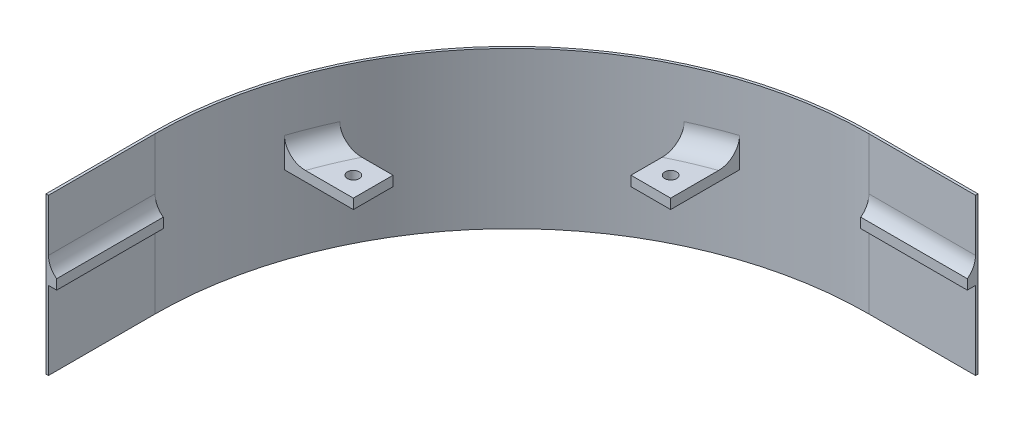
SolidWorks part; units mm, degrees
ref_plane "Front Plane" through (0, 0, 0) normal (0, 0, 1) x (1, 0, 0)
ref_plane "Top Plane" through (0, 0, 0) normal (0, 1, 0) x (1, 0, 0)
ref_plane "Right Plane" through (0, 0, 0) normal (1, 0, 0) x (0, 0, -1)
sketch "Sketch1" plane through (0, 0, 0) normal (0, 1, 0) x (1, 0, 0)
  line L1 (-34.1312, -148.4312) -> (34.1313, -148.4312)
  line L2 (-148.4312, -34.1312) -> (-148.4312, 34.1313)
  line L3 (-34.1312, 148.4313) -> (34.1313, 148.4313)
  line L4 (148.4312, -34.1312) -> (148.4312, 34.1313)
  line L5 (-148.4312, -148.4312) -> (148.4313, 148.4312) construction
  line L6 (-148.4312, 148.4312) -> (148.4313, -148.4312) construction
  arc A1 (-34.1312, -148.4312) -> (-148.4312, -34.1312) centre (-34.1312, -34.1312) cw
  arc A2 (34.1313, -148.4312) -> (148.4312, -34.1312) centre (34.1313, -34.1312) ccw
  arc A3 (34.1313, 148.4313) -> (148.4312, 34.1313) centre (34.1313, 34.1313) cw
  arc A4 (-148.4312, 34.1313) -> (-34.1312, 148.4313) centre (-34.1312, 34.1313) cw
  point P0 (0, 0)
  dimension "D1" = 296.8625
  dimension "D3" = 114.3
  dimension "D2" = 296.8625
extrude "Boss-Extrude1" add sketch "Sketch1" along normal blind 6.35
sketch "Sketch4" plane through (0, 6.35, 0) normal (0, 1, 0) x (1, 0, 0)
  line L0 (-39.448, -144.217) -> (39.448, -144.217)
  line L1 (-39.448, -120.2902) -> (39.448, -120.2902)
  line L2 (-39.448, 120.2902) -> (39.448, 120.2902)
  line L3 (-39.448, 144.217) -> (39.448, 144.217)
  line L4 (-39.448, 118.7027) -> (39.448, 118.7027)
  line L5 (-39.448, 145.8045) -> (39.448, 145.8045)
  line L6 (-39.448, -145.8045) -> (39.448, -145.8045)
  line L7 (-39.448, -118.7027) -> (39.448, -118.7027)
  line L8 (-13.125, 107.0625) -> (-13.125, 100.3125) construction
  line L9 (-13.125, 100.3125) -> (-18.875, 100.3125) construction
  line L10 (-18.875, 100.3125) -> (-18.875, 107.0625) construction
  line L11 (-18.875, 107.0625) -> (-13.125, 107.0625) construction
  line L12 (18.875, 107.0625) -> (18.875, 100.3125) construction
  line L13 (18.875, 100.3125) -> (13.125, 100.3125) construction
  line L14 (13.125, 100.3125) -> (13.125, 107.0625) construction
  line L15 (13.125, 107.0625) -> (18.875, 107.0625) construction
  line L16 (-7, 56.325) -> (-13, 56.325) construction
  line L17 (-13, 56.325) -> (-13, 64.325) construction
  line L18 (-13, 64.325) -> (-7, 64.325) construction
  line L19 (-7, 64.325) -> (-7, 56.325) construction
  line L20 (25, 56.325) -> (19, 56.325) construction
  line L21 (19, 56.325) -> (19, 64.325) construction
  line L22 (19, 64.325) -> (25, 64.325) construction
  line L23 (25, 64.325) -> (25, 56.325) construction
  line L24 (-13, -56.325) -> (-7, -56.325) construction
  line L25 (-7, -56.325) -> (-7, -64.325) construction
  line L26 (-7, -64.325) -> (-13, -64.325) construction
  line L27 (-13, -64.325) -> (-13, -56.325) construction
  line L28 (19, -56.325) -> (25, -56.325) construction
  line L29 (25, -56.325) -> (25, -64.325) construction
  line L30 (25, -64.325) -> (19, -64.325) construction
  line L31 (19, -64.325) -> (19, -56.325) construction
  line L32 (-18.875, -107.0625) -> (-18.875, -100.3125) construction
  line L33 (-18.875, -100.3125) -> (-13.125, -100.3125) construction
  line L34 (-13.125, -100.3125) -> (-13.125, -107.0625) construction
  line L35 (-13.125, -107.0625) -> (-18.875, -107.0625) construction
  line L36 (13.125, -107.0625) -> (13.125, -100.3125) construction
  line L37 (13.125, -100.3125) -> (18.875, -100.3125) construction
  line L38 (18.875, -100.3125) -> (18.875, -107.0625) construction
  line L39 (18.875, -107.0625) -> (13.125, -107.0625) construction
  line L40 (-13.125, 107.0625) -> (-13.125, 100.3125)
  line L41 (-13.125, 100.3125) -> (-18.875, 100.3125)
  line L42 (-18.875, 100.3125) -> (-18.875, 107.0625)
  line L43 (-18.875, 107.0625) -> (-13.125, 107.0625)
  line L44 (18.875, 107.0625) -> (18.875, 100.3125)
  line L45 (18.875, 100.3125) -> (13.125, 100.3125)
  line L46 (13.125, 100.3125) -> (13.125, 107.0625)
  line L47 (13.125, 107.0625) -> (18.875, 107.0625)
  line L48 (-7, 56.325) -> (-13, 56.325)
  line L49 (-13, 56.325) -> (-13, 64.325)
  line L50 (-13, 64.325) -> (-7, 64.325)
  line L51 (-7, 64.325) -> (-7, 56.325)
  line L52 (25, 56.325) -> (19, 56.325)
  line L53 (19, 56.325) -> (19, 64.325)
  line L54 (19, 64.325) -> (25, 64.325)
  line L55 (25, 64.325) -> (25, 56.325)
  line L56 (-13, -56.325) -> (-7, -56.325)
  line L57 (-7, -56.325) -> (-7, -64.325)
  line L58 (-7, -64.325) -> (-13, -64.325)
  line L59 (-13, -64.325) -> (-13, -56.325)
  line L60 (19, -56.325) -> (25, -56.325)
  line L61 (25, -56.325) -> (25, -64.325)
  line L62 (25, -64.325) -> (19, -64.325)
  line L63 (19, -64.325) -> (19, -56.325)
  line L64 (-18.875, -107.0625) -> (-18.875, -100.3125)
  line L65 (-18.875, -100.3125) -> (-13.125, -100.3125)
  line L66 (-13.125, -100.3125) -> (-13.125, -107.0625)
  line L67 (-13.125, -107.0625) -> (-18.875, -107.0625)
  line L68 (13.125, -107.0625) -> (13.125, -100.3125)
  line L69 (13.125, -100.3125) -> (18.875, -100.3125)
  line L70 (18.875, -100.3125) -> (18.875, -107.0625)
  line L71 (18.875, -107.0625) -> (13.125, -107.0625)
  line L72 (-18.875, -107.0625) -> (-13.125, -100.3125) construction
  line L73 (13.125, -107.0625) -> (18.875, -100.3125) construction
  line L74 (-13, -64.325) -> (-7, -56.325) construction
  line L75 (19, -64.325) -> (25, -56.325) construction
  line L76 (-13, 56.325) -> (-7, 64.325) construction
  line L77 (19, 56.325) -> (25, 64.325) construction
  line L78 (13.125, 100.3125) -> (18.875, 107.0625) construction
  line L79 (-18.875, 100.3125) -> (-13.125, 107.0625) construction
  arc A0 (58.6792, -125.8296) -> (39.448, -120.2902) centre (39.448, -156.4424) ccw construction
  arc A1 (58.6792, -138.6776) -> (58.6792, -125.8296) centre (54.6436, -132.2536) ccw construction
  arc A2 (39.448, -144.217) -> (58.6792, -138.6776) centre (39.448, -108.0647) ccw construction
  arc A3 (-39.448, -120.2902) -> (-58.6792, -125.8296) centre (-39.448, -156.4424) ccw construction
  arc A4 (-58.6792, -125.8296) -> (-58.6792, -138.6776) centre (-54.6436, -132.2536) ccw construction
  arc A5 (-58.6792, -138.6776) -> (-39.448, -144.217) centre (-39.448, -108.0647) ccw construction
  arc A6 (-58.6792, 125.8296) -> (-39.448, 120.2902) centre (-39.448, 156.4424) ccw construction
  arc A7 (-58.6792, 138.6776) -> (-58.6792, 125.8296) centre (-54.6436, 132.2536) ccw construction
  arc A8 (-39.448, 144.217) -> (-58.6792, 138.6776) centre (-39.448, 108.0647) ccw construction
  arc A9 (58.6792, 138.6776) -> (39.448, 144.217) centre (39.448, 108.0647) ccw construction
  arc A10 (58.6792, 125.8296) -> (58.6792, 138.6776) centre (54.6436, 132.2536) ccw construction
  arc A11 (39.448, 120.2902) -> (58.6792, 125.8296) centre (39.448, 156.4424) ccw construction
  arc A12 (58.6792, -125.8296) -> (39.448, -120.2902) centre (39.448, -156.4424) ccw
  arc A13 (58.6792, -138.6776) -> (58.6792, -125.8296) centre (54.6436, -132.2536) ccw
  arc A14 (39.448, -144.217) -> (58.6792, -138.6776) centre (39.448, -108.0647) ccw
  arc A15 (-39.448, -120.2902) -> (-58.6792, -125.8296) centre (-39.448, -156.4424) ccw
  arc A16 (-58.6792, -125.8296) -> (-58.6792, -138.6776) centre (-54.6436, -132.2536) ccw
  arc A17 (-58.6792, -138.6776) -> (-39.448, -144.217) centre (-39.448, -108.0647) ccw
  arc A18 (-58.6792, 125.8296) -> (-39.448, 120.2902) centre (-39.448, 156.4424) ccw
  arc A19 (-58.6792, 138.6776) -> (-58.6792, 125.8296) centre (-54.6436, 132.2536) ccw
  arc A20 (-39.448, 144.217) -> (-58.6792, 138.6776) centre (-39.448, 108.0647) ccw
  arc A21 (58.6792, 138.6776) -> (39.448, 144.217) centre (39.448, 108.0647) ccw
  arc A22 (58.6792, 125.8296) -> (58.6792, 138.6776) centre (54.6436, 132.2536) ccw
  arc A23 (39.448, 120.2902) -> (58.6792, 125.8296) centre (39.448, 156.4424) ccw
  arc A24 (-59.5236, 124.4853) -> (-39.448, 118.7027) centre (-39.448, 156.4424) ccw
  arc A25 (39.448, 118.7027) -> (59.5236, 124.4853) centre (39.448, 156.4424) ccw
  arc A26 (59.5236, 124.4853) -> (59.5236, 140.0219) centre (54.6436, 132.2536) ccw
  arc A27 (59.5236, 140.0219) -> (39.448, 145.8045) centre (39.448, 108.0647) ccw
  arc A28 (-39.448, 145.8045) -> (-59.5236, 140.0219) centre (-39.448, 108.0647) ccw
  arc A29 (-59.5236, 140.0219) -> (-59.5236, 124.4853) centre (-54.6436, 132.2536) ccw
  arc A30 (39.448, -145.8045) -> (59.5236, -140.0219) centre (39.448, -108.0647) ccw
  arc A31 (59.5236, -140.0219) -> (59.5236, -124.4853) centre (54.6436, -132.2536) ccw
  arc A32 (59.5236, -124.4853) -> (39.448, -118.7027) centre (39.448, -156.4424) ccw
  arc A33 (-39.448, -118.7027) -> (-59.5236, -124.4853) centre (-39.448, -156.4424) ccw
  arc A34 (-59.5236, -124.4853) -> (-59.5236, -140.0219) centre (-54.6436, -132.2536) ccw
  arc A35 (-59.5236, -140.0219) -> (-39.448, -145.8045) centre (-39.448, -108.0647) ccw
  point P58 (-16, -103.6875)
  point P60 (16, 103.6875)
  point P62 (-16, 103.6875)
  point P63 (-10, 60.325)
  point P66 (22, 60.325)
  point P68 (-10, -60.325)
  point P70 (16, -103.6875)
  point P71 (22, -60.325)
  dimension "D1" = 1.5875
extrude "Cut-Extrude1" cut sketch "Sketch4" against normal blind 6.35 contours L2 A23 A22 A21 L3 A20 A19 A18 | A28 A29 A24 L4 A25 A26 A27 L5 A23 L2 A18 A19 A20 L3 A21 A22 | A16 A17 L0 A14 A13 A12 L1 A15 | A34 A35 L6 A30 A31 A32 L7 A33 A17 A16 A15 L1 A12 A13 A14 L0 region at (0, 6.35, 132.2536) region at (0, 6.35, -132.2536) region at (-49.5328, 6.35, -121.431) region at (-49.5328, 6.35, 143.0762)
hole_wizard "M4 Clearance Hole1" positions "Sketch7" profile "Sketch9" hole size "M4" standard "ANSI Metric" end condition through all
sketch "Sketch7" plane through (0, 6.35, 0) normal (0, 1, 0) x (1, 0, 0)
  point P0 (-16, -103.6875)
  point P3 (16, -103.6875)
  point P6 (22, -60.325)
  point P9 (-10, -60.325)
  point P12 (-10, 60.325)
  point P15 (22, 60.325)
  point P18 (16, 103.6875)
  point P21 (-16, 103.6875)
sketch "Sketch9" plane through (-16, 6.35, 103.6875) normal (1, 0, 0) x (0, 0, 1)
  line L0 (0, 0) -> (0, 6.35)
  line L1 (0, 6.35) -> (2.25, 6.35)
  line L2 (2.25, 6.35) -> (2.25, 0)
  line L5 (2.25, 0) -> (0, 0)
  line L11 (0, -6.35) -> (0, 107.95) construction
  dimension "Thru Hole Dia." = 4.5
  dimension "Thru Hole Depth" = 6.35
sketch "Sketch11" plane through (0, 6.35, 0) normal (0, 1, 0) x (1, 0, 0)
  line L1 (101.6, 101.6) -> (-101.6, 101.6)
  line L2 (101.6, 101.6) -> (101.6, -101.6)
  line L3 (101.6, -101.6) -> (-101.6, -101.6)
  line L4 (-101.6, 101.6) -> (-101.6, -101.6)
  line L5 (101.6, 101.6) -> (-101.6, -101.6) construction
  line L6 (101.6, -101.6) -> (-101.6, 101.6) construction
  circle A0 centre (0, 0) radius 143.6841 construction
  point P7 (-127, -101.6)
  point P10 (-127, 101.6)
  point P11 (-127, -76.2)
  point P12 (-127, -50.8)
  point P13 (-127, -25.4)
  point P14 (-127, 0)
  point P15 (-127, 25.4)
  point P16 (-127, 50.8)
  point P17 (-127, 76.2)
  point P18 (-101.6, -101.6)
  point P19 (-101.6, 101.6)
  point P20 (-101.6, -76.2)
  point P21 (-101.6, -50.8)
  point P22 (-101.6, -25.4)
  point P23 (-101.6, 0)
  point P24 (-101.6, 25.4)
  point P25 (-101.6, 50.8)
  point P26 (-101.6, 76.2)
  point P27 (-76.2, -101.6)
  point P28 (-76.2, 101.6)
  point P29 (-76.2, -76.2)
  point P30 (-76.2, -50.8)
  point P31 (-76.2, -25.4)
  point P32 (-76.2, 0)
  point P33 (-76.2, 25.4)
  point P34 (-76.2, 50.8)
  point P35 (-76.2, 76.2)
  point P36 (-50.8, -101.6)
  point P37 (-50.8, 101.6)
  point P38 (-50.8, -76.2)
  point P39 (-50.8, -50.8)
  point P40 (-50.8, -25.4)
  point P41 (-50.8, 0)
  point P42 (-50.8, 25.4)
  point P43 (-50.8, 50.8)
  point P44 (-50.8, 76.2)
  point P45 (-25.4, -101.6)
  point P46 (-25.4, 101.6)
  point P47 (-25.4, -76.2)
  point P48 (-25.4, -50.8)
  point P49 (-25.4, -25.4)
  point P50 (-25.4, 0)
  point P51 (-25.4, 25.4)
  point P52 (-25.4, 50.8)
  point P53 (-25.4, 76.2)
  point P54 (0, -101.6)
  point P55 (0, 101.6)
  point P56 (0, -76.2)
  point P57 (0, -50.8)
  point P58 (0, -25.4)
  point P59 (0, 0)
  point P60 (0, 25.4)
  point P61 (0, 50.8)
  point P62 (0, 76.2)
  point P63 (25.4, -101.6)
  point P64 (25.4, 101.6)
  point P65 (25.4, -76.2)
  point P66 (25.4, -50.8)
  point P67 (25.4, -25.4)
  point P68 (25.4, 0)
  point P69 (25.4, 25.4)
  point P70 (25.4, 50.8)
  point P71 (25.4, 76.2)
  point P72 (50.8, -101.6)
  point P73 (50.8, 101.6)
  point P74 (50.8, -76.2)
  point P75 (50.8, -50.8)
  point P76 (50.8, -25.4)
  point P77 (50.8, 0)
  point P78 (50.8, 25.4)
  point P79 (50.8, 50.8)
  point P80 (50.8, 76.2)
  point P81 (76.2, -101.6)
  point P82 (76.2, 101.6)
  point P83 (76.2, -76.2)
  point P84 (76.2, -50.8)
  point P85 (76.2, -25.4)
  point P86 (76.2, 0)
  point P87 (76.2, 25.4)
  point P88 (76.2, 50.8)
  point P89 (76.2, 76.2)
  point P90 (101.6, -101.6)
  point P91 (101.6, 101.6)
  point P92 (101.6, -76.2)
  point P93 (101.6, -50.8)
  point P94 (101.6, -25.4)
  point P95 (101.6, 0)
  point P96 (101.6, 25.4)
  point P97 (101.6, 50.8)
  point P98 (101.6, 76.2)
  point P99 (127, -101.6)
  point P100 (127, 101.6)
  point P101 (127, -76.2)
  point P102 (127, -50.8)
  point P103 (127, -25.4)
  point P104 (127, 0)
  point P105 (127, 25.4)
  point P106 (127, 50.8)
  point P107 (127, 76.2)
  dimension "D1" = 203.2
  dimension "D2" = 25.4
  dimension "D3" = 11
  dimension "D4" = 9
hole_wizard "#6 Clearance Hole1" positions "Sketch12" profile "Sketch13" hole size "#6" standard "ANSI Inch" end condition through all
sketch "Sketch12" plane through (0, 6.35, 0) normal (0, 1, 0) x (1, 0, 0)
  point P0 (-101.6, -101.6)
  point P3 (-101.6, 101.6)
  point P6 (101.6, 101.6)
  point P9 (101.6, -101.6)
  point P12 (-127, -76.2)
  point P15 (-127, -50.8)
  point P18 (-127, 50.8)
  point P21 (-127, 76.2)
  point P24 (-101.6, 76.2)
  point P27 (-101.6, 50.8)
  point P30 (-101.6, 25.4)
  point P33 (-101.6, 0)
  point P36 (-101.6, -25.4)
  point P39 (-101.6, -50.8)
  point P42 (-101.6, -76.2)
  point P45 (-76.2, -101.6)
  point P48 (-50.8, -101.6)
  point P51 (-50.8, -76.2)
  point P54 (-76.2, -76.2)
  point P57 (-76.2, -50.8)
  point P60 (-50.8, -50.8)
  point P63 (-50.8, -25.4)
  point P66 (-76.2, -25.4)
  point P69 (-76.2, 0)
  point P72 (-50.8, 0)
  point P75 (-50.8, 25.4)
  point P78 (-76.2, 25.4)
  point P81 (-76.2, 50.8)
  point P84 (-50.8, 50.8)
  point P87 (-50.8, 76.2)
  point P90 (-76.2, 76.2)
  point P93 (-76.2, 101.6)
  point P96 (-50.8, 101.6)
  point P99 (50.8, -101.6)
  point P102 (76.2, -101.6)
  point P105 (101.6, -76.2)
  point P108 (127, -76.2)
  point P111 (127, -50.8)
  point P114 (101.6, -25.4)
  point P117 (101.6, -50.8)
  point P120 (76.2, -25.4)
  point P123 (76.2, -50.8)
  point P126 (76.2, -76.2)
  point P129 (50.8, -76.2)
  point P132 (50.8, -50.8)
  point P135 (50.8, -25.4)
  point P138 (50.8, 0)
  point P141 (76.2, 0)
  point P144 (101.6, 0)
  point P147 (101.6, 25.4)
  point P150 (101.6, 50.8)
  point P153 (101.6, 76.2)
  point P156 (127, 50.8)
  point P159 (127, 76.2)
  point P162 (76.2, 101.6)
  point P165 (50.8, 101.6)
  point P168 (50.8, 76.2)
  point P171 (76.2, 76.2)
  point P174 (76.2, 50.8)
  point P177 (76.2, 25.4)
  point P180 (50.8, 25.4)
  point P183 (50.8, 50.8)
  point P186 (0, 0)
  point P189 (-25.4, -25.4)
  point P192 (-25.4, 0)
  point P195 (-25.4, 25.4)
  point P198 (0, 25.4)
  point P201 (25.4, 25.4)
  point P204 (25.4, 0)
  point P207 (25.4, -25.4)
  point P210 (0, -25.4)
  point P213 (127, -25.4)
  point P216 (127, 0)
  point P219 (127, 25.4)
  point P222 (-127, -25.4)
  point P225 (-127, 0)
  point P228 (-127, 25.4)
sketch "Sketch13" plane through (-101.6, 6.35, 101.6) normal (1, 0, 0) x (0, 0, 1)
  line L0 (0, 0) -> (0, 6.35)
  line L1 (0, 6.35) -> (1.8986, 6.35)
  line L2 (1.8986, 6.35) -> (1.8986, 0)
  line L5 (1.8986, 0) -> (0, 0)
  line L11 (0, -6.35) -> (0, 107.95) construction
  dimension "Thru Hole Dia." = 3.7973
  dimension "Thru Hole Depth" = 6.35
sketch "Sketch14" plane through (0, 6.35, 0) normal (0, 1, 0) x (1, 0, 0)
  line L1 (76.2, -127) -> (-76.2, -127)
  line L2 (76.2, -127) -> (76.2, 127)
  line L3 (76.2, 127) -> (-76.2, 127)
  line L4 (-76.2, -127) -> (-76.2, 127)
  line L5 (76.2, -127) -> (-76.2, 127) construction
  line L6 (76.2, 127) -> (-76.2, -127) construction
  circle A1 centre (-76.2, -101.6) radius 1.8986 construction
  circle A2 centre (-101.6, -101.6) radius 1.8986 construction
  point P0 (0, 0)
  dimension "D1" = 25.4
  dimension "D2" = 25.4
hole_wizard "#6 Clearance Hole2" positions "Sketch15" profile "Sketch16" hole size "#6" standard "ANSI Inch" end condition through all
sketch "Sketch15" plane through (0, 6.35, 0) normal (0, 1, 0) x (1, 0, 0)
  point P0 (-76.2, -127)
  point P3 (76.2, -127)
  point P6 (76.2, 127)
  point P9 (-76.2, 127)
sketch "Sketch16" plane through (-76.2, 6.35, 127) normal (1, 0, 0) x (0, 0, 1)
  line L0 (0, 0) -> (0, 6.35)
  line L1 (0, 6.35) -> (1.8986, 6.35)
  line L2 (1.8986, 6.35) -> (1.8986, 0)
  line L5 (1.8986, 0) -> (0, 0)
  line L11 (0, -6.35) -> (0, 107.95) construction
  dimension "Thru Hole Dia." = 3.7973
  dimension "Thru Hole Depth" = 6.35
sketch "Sketch29" plane through (0, 6.35, 0) normal (0, 1, 0) x (1, 0, 0)
  line L0 (-39.448, 145.8045) -> (39.448, 145.8045) construction
  line L1 (-148.4312, 34.1312) -> (-148.4312, -34.1312) construction
  line L2 (-34.1312, 148.4313) -> (0, 148.4313)
  line L3 (34.1313, 148.4313) -> (-34.1312, 148.4313) construction
  line L4 (-148.4312, 34.1312) -> (-148.4312, 0)
  line L5 (0, 148.4313) -> (-34.1312, 148.4313)
  line L6 (-69.85, 142.7068) -> (-69.85, 120.65)
  line L7 (-69.85, 120.65) -> (-82.55, 120.65)
  line L8 (-82.55, 120.65) -> (-82.55, 137.6692)
  line L9 (-137.6692, 82.55) -> (-120.65, 82.55)
  line L10 (-34.1312, -148.4312) -> (34.1313, -148.4312)
  line L11 (148.4313, -34.1312) -> (148.4312, 34.1313)
  line L12 (34.1313, 148.4313) -> (-34.1312, 148.4313)
  line L13 (-148.4312, 34.1312) -> (-148.4312, -34.1312)
  line L14 (-34.1312, 148.4313) -> (-34.1312, 145.8045)
  line L15 (-34.1312, 145.8045) -> (0, 145.8045)
  line L16 (0, 148.4313) -> (-34.1312, 148.4313)
  line L17 (-148.4312, 34.1312) -> (-148.4312, 0)
  line L18 (-120.65, 82.55) -> (-120.65, 69.85)
  line L19 (-120.65, 69.85) -> (-142.7068, 69.85)
  line L20 (0, 149.225) -> (-34.1312, 149.225)
  line L21 (-149.225, 34.1312) -> (-149.225, 0)
  line L22 (0, 148.4313) -> (0, 149.225)
  line L23 (-148.4312, 0) -> (-149.225, 0)
  line L24 (34.1313, 149.225) -> (-34.1312, 149.225) construction
  line L25 (34.1313, 148.4313) -> (-34.1312, 148.4313) construction
  line L26 (-149.225, 34.1312) -> (-149.225, -34.1312) construction
  line L27 (-148.4312, 34.1312) -> (-148.4312, -34.1312) construction
  line L28 (0, 148.4313) -> (0, 145.8045)
  line L30 (-148.4312, 34.1312) -> (-145.8045, 34.1312)
  line L31 (-148.4312, 34.1312) -> (-148.4312, 0)
  line L32 (-148.4312, 0) -> (-145.8045, 0)
  line L33 (-145.8045, 34.1312) -> (-145.8045, 0)
  arc A0 (-34.1312, 148.4313) -> (-148.4312, 34.1312) centre (-34.1312, 34.1313) ccw construction
  arc A1 (-34.1312, 148.4313) -> (-69.85, 142.7068) centre (-34.1312, 34.1313) ccw
  circle A2 centre (-127, 76.2) radius 1.8987 construction
  circle A3 centre (-76.2, 127) radius 1.8987 construction
  circle A4 centre (-127, 76.2) radius 1.8987
  circle A5 centre (-76.2, 127) radius 1.8987
  arc A6 (-34.1312, 149.225) -> (-149.225, 34.1313) centre (-34.1312, 34.1313) ccw
  arc A7 (-82.55, 137.6692) -> (-137.6692, 82.55) centre (-34.1312, 34.1313) ccw
  arc A8 (-34.1312, 148.4313) -> (-148.4312, 34.1312) centre (-34.1312, 34.1313) ccw construction
  arc A9 (-82.55, 137.6692) -> (-137.6692, 82.55) centre (-34.1312, 34.1313) ccw
  arc A10 (-148.4312, -34.1312) -> (-34.1312, -148.4312) centre (-34.1312, -34.1312) ccw
  arc A11 (34.1313, -148.4312) -> (148.4313, -34.1312) centre (34.1313, -34.1312) ccw
  arc A12 (148.4312, 34.1313) -> (34.1313, 148.4313) centre (34.1313, 34.1313) ccw
  arc A13 (-34.1312, 148.4313) -> (-148.4312, 34.1312) centre (-34.1312, 34.1313) ccw
  arc A14 (-142.7068, 69.85) -> (-148.4312, 34.1312) centre (-34.1312, 34.1313) ccw
  arc A15 (-142.7068, 69.85) -> (-148.4312, 34.1312) centre (-34.1312, 34.1313) ccw
  arc A16 (-34.1312, 148.4313) -> (-148.4312, 34.1312) centre (-34.1312, 34.1313) ccw
  arc A17 (-34.1312, 148.4313) -> (-69.85, 142.7068) centre (-34.1312, 34.1313) ccw
  point P31 (-76.2, 120.65)
  point P32 (-120.65, 76.2)
  dimension "D3" = 6.35
  dimension "D2" = 6.35
  dimension "D4" = 6.35
  dimension "D5" = 6.35
  dimension "D1" = 0
  dimension "D6" = 0.7937
sketch "Sketch30" plane through (0, 6.35, 0) normal (0, 1, 0) x (1, 0, 0)
  line L4 (-34.1312, -148.4312) -> (34.1313, -148.4312)
  line L5 (148.4313, -34.1312) -> (148.4312, 34.1313)
  line L6 (34.1313, 148.4313) -> (-34.1312, 148.4313)
  line L7 (-148.4312, 34.1313) -> (-148.4312, -34.1312)
  line L8 (-34.1312, -148.4312) -> (34.1313, -148.4312)
  line L9 (148.4313, -34.1312) -> (148.4312, 34.1313)
  line L10 (34.1313, 148.4313) -> (-34.1312, 148.4313)
  line L11 (-148.4312, 34.1313) -> (-148.4312, -34.1312)
  arc A4 (-148.4312, -34.1312) -> (-34.1312, -148.4312) centre (-34.1312, -34.1312) ccw
  arc A5 (34.1313, -148.4312) -> (148.4313, -34.1312) centre (34.1313, -34.1312) ccw
  arc A6 (148.4312, 34.1313) -> (34.1313, 148.4313) centre (34.1313, 34.1313) ccw
  arc A7 (-34.1312, 148.4313) -> (-148.4312, 34.1313) centre (-34.1312, 34.1313) ccw
  arc A8 (-148.4312, -34.1312) -> (-34.1312, -148.4312) centre (-34.1312, -34.1312) ccw
  arc A9 (34.1313, -148.4312) -> (148.4313, -34.1312) centre (34.1313, -34.1312) ccw
  arc A10 (148.4312, 34.1313) -> (34.1313, 148.4313) centre (34.1313, 34.1313) ccw
  arc A11 (-34.1312, 148.4313) -> (-148.4312, 34.1313) centre (-34.1312, 34.1313) ccw
  dimension "D1" = 0
extrude "Boss-Extrude4" add sketch "Sketch29" along normal blind 3.175 contours L6 A16 L8 L7 A5 | L9 A16 L19 L18 A4 | L33 L30 L4 L32 | L28 L2 L14 L15 region at (-17.0656, 6.35, -147.1179) region at (-75.9165, 6.35, -130.7143) region at (-130.7143, 6.35, -75.9165) region at (-147.1179, 6.35, -17.0656)
extrude "Cut-Extrude9" cut sketch "Sketch30" against normal through all
extrude "Boss-Extrude5" add sketch "Sketch29<7>" against normal blind 25 and the other way blind 25 contours A16 A1 L5 L22 L20 A6 L21 L23 L4 A14 A7 region at (-52.2519, 6.35, -147.1995)
sketch "Sketch29<7>" plane through (0, 6.35, 0) normal (0, 1, 0) x (1, 0, 0) same geometry as "Sketch29"
sketch "Sketch31" plane through (-145.8045, 0, 0) normal (1, 0, 0) x (0, 0, -1)
  line L4 (0, 6.35) -> (34.1312, 6.35)
  line L5 (34.1312, 6.35) -> (34.1312, 9.525)
  line L6 (34.1312, 9.525) -> (0, 9.525)
  line L7 (0, 9.525) -> (0, 6.35)
  line L8 (0, 6.35) -> (34.1312, 6.35)
  line L9 (34.1312, 6.35) -> (34.1312, 9.525)
  line L10 (34.1312, 9.525) -> (0, 9.525)
  line L11 (0, 9.525) -> (0, 6.35)
  dimension "D1" = 0
extrude "Boss-Extrude6" add sketch "Sketch31" against normal up to surface (3.4205 mm away) up to face at (-149.225, 6.35, -17.0656)
sketch "Sketch32" plane through (0, 0, -145.8045) normal (0, 0, 1) x (1, 0, 0)
  line L4 (-34.1313, 6.35) -> (0, 6.35)
  line L5 (0, 6.35) -> (0, 9.525)
  line L6 (0, 9.525) -> (-34.1313, 9.525)
  line L7 (-34.1313, 9.525) -> (-34.1313, 6.35)
  line L8 (-34.1313, 6.35) -> (0, 6.35)
  line L9 (0, 6.35) -> (0, 9.525)
  line L10 (0, 9.525) -> (-34.1313, 9.525)
  line L11 (-34.1313, 9.525) -> (-34.1313, 6.35)
  dimension "D1" = 0
extrude "Boss-Extrude7" add sketch "Sketch32" against normal up to surface (3.4205 mm away) up to face at (-17.0656, 6.35, -149.225)
fillet "Fillet2" radius 6.35 2 edges at (-76.2753, 9.525, -140.378) (-140.378, 9.525, -76.2753)
fillet "Fillet3" radius 6.35 2 edges at (-17.0656, 9.525, -148.4313) (-148.4312, 9.525, -17.0656)
